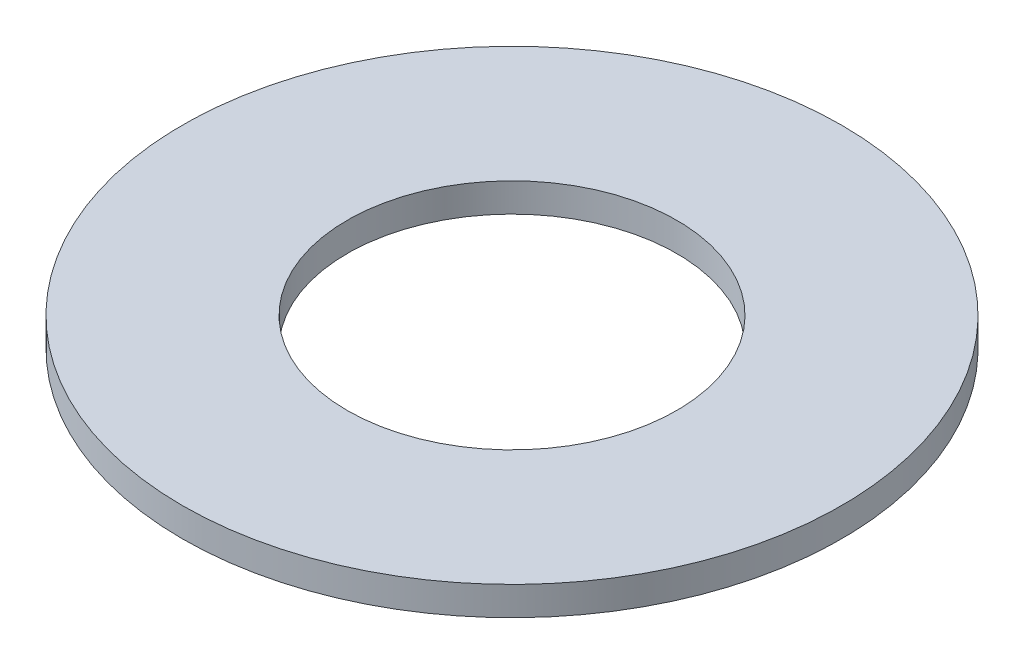
SolidWorks part; units mm, degrees
ref_plane "Front Plane" through (0, 0, 0) normal (0, 0, 1) x (1, 0, 0)
ref_plane "Top Plane" through (0, 0, 0) normal (0, 1, 0) x (1, 0, 0)
ref_plane "Right Plane" through (0, 0, 0) normal (1, 0, 0) x (0, 0, -1)
sketch "Sketch1" plane through (0, 0, 0) normal (0, 1, 0) x (1, 0, 0)
  circle A0 centre (0, 0) radius 80
  dimension "FLANGE_OD" = 160
extrude "Boss-Extrude1" add sketch "Sketch1" along normal blind 7
sketch "Sketch2" plane through (0, 0, 0) normal (0, 1, 0) x (1, 0, 0)
  circle A0 centre (0, 0) radius 40
  dimension "BORE_D" = 80
extrude "Cut-Extrude1" cut sketch "Sketch2" along normal through all
sketch "Sketch3" plane through (0, 7, 0) normal (0, 1, 0) x (1, 0, 0)
  circle A0 centre (0, 0) radius 37.1948 construction
  circle A1 centre (-37.1948, 0) radius 2.4138
  dimension "BOLT_D" = 4.8276
  dimension "BOLT_PCD" = 74.3897
extrude "Cut-Extrude2" cut sketch "Sketch3" against normal blind 5.0167 rebuild error yes
pattern_circular "CirPattern1" count 3 over 360 rebuild error yes
